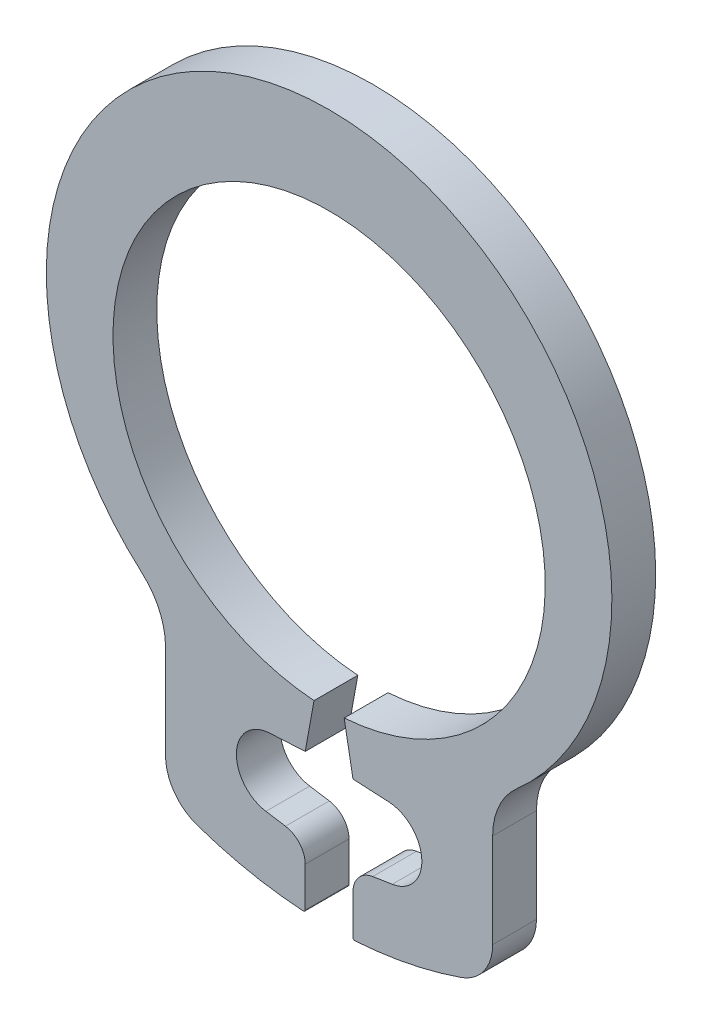
SolidWorks part; units mm, degrees
ref_plane "Front" through (0, 0, 0) normal (0, 0, 1) x (1, 0, 0)
ref_plane "Top" through (0, 0, 0) normal (0, 1, 0) x (1, 0, 0)
ref_plane "Right" through (0, 0, 0) normal (1, 0, 0) x (0, 0, -1)
sketch "Sketch1" plane through (0, 0, 0) normal (0, 0, 1) x (1, 0, 0)
  line L0 (0, 0) -> (-3.2043, -1.85) construction
  line L1 (0, 6.9) -> (0, -6.9) construction
  line L2 (-2.8001, -6.3247) -> (-2.8001, -3.591) construction
  line L3 (-4, 3.8) -> (4, 3.8) construction
  line L4 (-2.8001, -3.591) -> (-3.1976, -4.1007) construction
  line L5 (-2.8001, -3.591) -> (0, 0) construction
  line L6 (0, 3.7) -> (0, 5.2) construction
  line L7 (0, 5.2) -> (0, 4.45) construction
  line L8 (0, -3.7) -> (0, -6.9) construction
  line L9 (-1.6663, -6.7131) -> (0, 0) construction
  line L10 (0, 0) -> (-0.4825, -6.9) construction
  line L11 (-2.8001, -6.3247) -> (0, 0) construction
  line L14 (-0.8914, -3.591) -> (-1.6663, -6.7131) construction
  line L15 (-1.2788, -5.1521) -> (-0.6965, -5.2966) construction
  arc A0 (0, 5.2) -> (-2.8001, -3.591) centre (0, 0.3585) ccw construction
  circle A2 centre (0, 0) radius 5.2 construction
  arc A3 (-2.8001, -6.3247) -> (-0.4825, -6.9) centre (0, 0) ccw construction
  circle A4 centre (0, 0) radius 3.7 construction
  circle A6 centre (-1.2788, -5.1521) radius 0.6 construction
  circle A9 centre (0, 0) radius 3.8 construction
  point P5 (-3.2043, -1.85)
  point P16 (0, 3.8)
  point P24 (-2.1051, -4.7548)
  point P35 (0, 5.2)
  point P36 (0, 3.7)
  point P37 (0, -3.7)
  point P38 (0, -6.9)
  dimension "Hole Diameter" = 1.2
  dimension "Max Sec." = 1.5
  dimension "Lug Height" = 3.2
  dimension "D6" = 4
  dimension "D3" = 120
  dimension "Ring ID" = 7.4
  dimension "For OD" = 8
  dimension "D2" = 2.4
sketch "Sketch2" plane through (0, 0, 0) normal (0, 1, 0) x (1, 0, 0)
  line L0 (-4.8282, 0.4) -> (-4.8282, -0.4) construction
  line L1 (0, 0) -> (-4.8282, 0) construction
  line L2 (0, 0.4) -> (0, -0.4) construction
  line L3 (0, 0) -> (4.8282, 0) construction
  line L4 (-5.2, 0) -> (5.2, 0) construction
  point P3 (-4.8282, 0)
  point P6 (0, 0)
  point P12 (4.8282, 0.45)
  dimension "Ring Thickness" = 0.8
sketch "Sketch3" plane through (0, 0, 0) normal (0, 0, 1) x (1, 0, 0)
  line L0 (-2.8001, -6.3247) -> (-2.8001, -3.591) construction
  line L1 (-2.8001, -5.7806) -> (-2.8001, -4.169)
  line L2 (0, 5.2) -> (0, 3.7)
  line L3 (-0.4092, -6.8707) -> (-0.4092, -6.1928)
  line L4 (0, 0) -> (-0.4825, -6.9) construction
  line L5 (-1.0191, -4.5529) -> (-0.4092, -4.5209)
  line L6 (-1.0815, -5.7447) -> (-0.7466, -5.7977)
  line L8 (-0.4092, -4.5209) -> (-0.2581, -3.691)
  line L9 (0.568, 0) -> (-0.568, 0) construction
  line L11 (-1.2788, -5.1521) -> (-0.6965, -5.2966) construction
  arc A0 (0, 5.2) -> (-2.8001, -3.591) centre (0, 0.3585) ccw construction
  arc A1 (-2.8001, -6.3247) -> (-0.4092, -6.9047) centre (0, 0) ccw construction
  arc A4 (0, 5.2) -> (-3.2056, -3.2697) centre (0, 0.3585) ccw
  arc A5 (-2.2617, -6.5366) -> (-0.4432, -6.9026) centre (0, 0) ccw
  arc A6 (-1.0191, -4.5529) -> (-1.0815, -5.7447) centre (-0.9877, -5.1521) ccw
  circle A7 centre (0, 0) radius 3.7 construction
  arc A8 (0, 3.7) -> (-0.2581, -3.691) centre (0, 0) ccw
  arc A9 (-3.2056, -3.2697) -> (-2.8001, -4.169) centre (-4.0001, -4.169) cw
  arc A10 (-2.8001, -5.7806) -> (-2.2617, -6.5366) centre (-2.0001, -5.7806) ccw
  circle A11 centre (-1.2788, -5.1521) radius 0.6 construction
  arc A12 (-0.7466, -5.7977) -> (-0.4092, -6.1928) centre (-0.8092, -6.1928) cw
  arc A13 (-0.4432, -6.9026) -> (-0.4092, -6.8707) centre (-0.4412, -6.8707) ccw
  point P37 (-0.9877, -5.2244)
  point P40 (-0.4092, -5.8512)
  dimension "D3" = 1.2
  dimension "D4" = 0.8
  dimension "D5" = 0.4
  dimension "D6" = 0.032
  dimension "D1" = 3
  dimension "D2" = 12
extrude "Boss-Extrude1" add sketch "Sketch3" along normal mid plane 0.75
fillet "Fillet1" [suppressed] type full round
mirror "Mirror1" about plane through (0, 5.2, 0.375) normal (-1, 0, 0) of bodies 109
dome "Dome1" [suppressed] faces to dome 2 distance 0.025 parameters "D1"=0.025
fillet "Fillet2" [suppressed] radius 0.032
equation "\"D1@Boss-Extrude1\" = \"Ring Thickness@Sketch5\""
equation "\"D2@Sketch1\"=\"Hole Diameter@Sketch1\"*2"
equation "\"D3@Sketch3\" = \"Lug Height@Sketch1\" * .375"
equation "\"D4@Sketch3\" = \"Lug Height@Sketch1\" * .25"
equation "\"D5@Sketch3\" = \"Lug Height@Sketch1\" * .125"
equation "\"D6@Sketch3\" = \"Lug Height@Sketch1\" * .01"
equation "\"D1@Dome1\" =  ( \"Ring Thickness@Sketch2\" - \"D1@Boss-Extrude1\" )  * .5"
equation "\"D1@Fillet2\" = \"Lug Height@Sketch1\" * .01"
